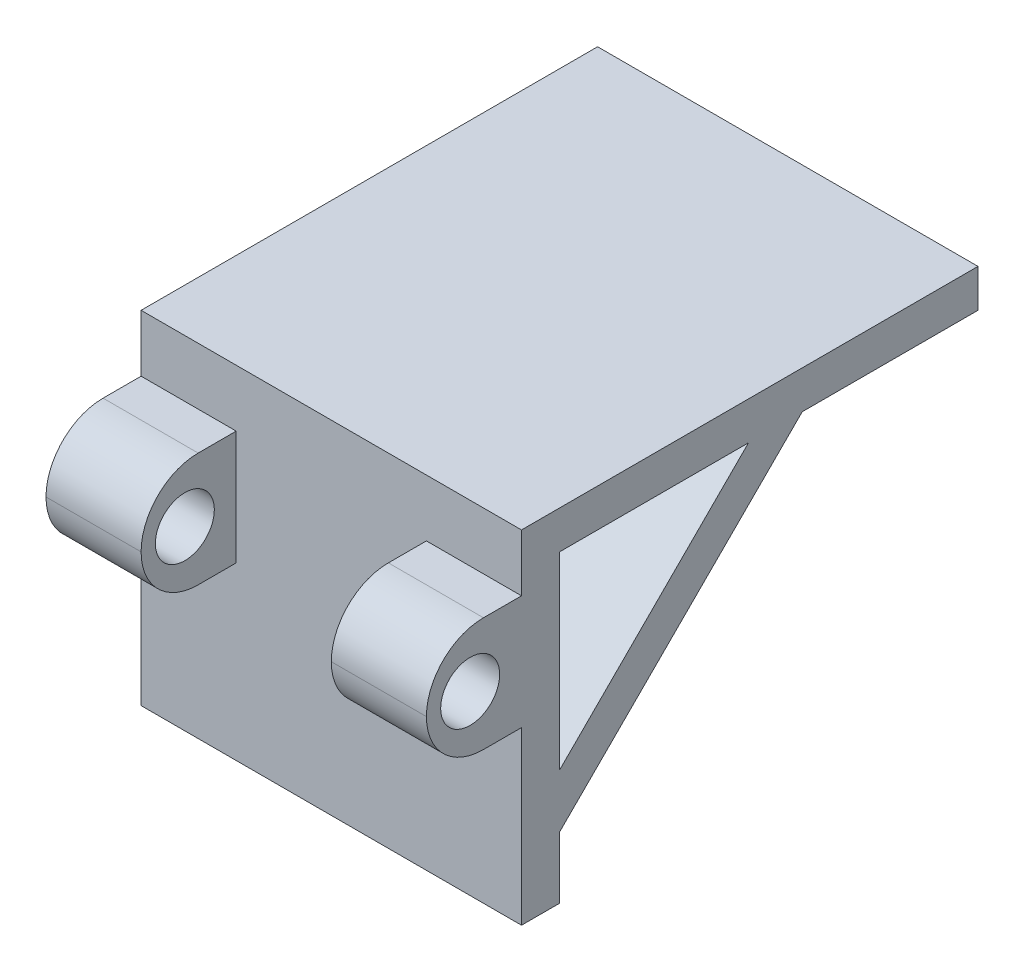
SolidWorks part; units mm, degrees
ref_plane "Front Plane" through (0, 0, 0) normal (0, 0, 1) x (1, 0, 0)
ref_plane "Top Plane" through (0, 0, 0) normal (0, 1, 0) x (1, 0, 0)
ref_plane "Right Plane" through (0, 0, 0) normal (1, 0, 0) x (0, 0, -1)
sketch "Sketch1" plane through (0, 0, 0) normal (0, 0, 1) x (1, 0, 0)
  line L0 (0, 0) -> (0, 7.5) construction
  line L1 (-10, -7.5) -> (10, -7.5)
  line L2 (-10, -7.5) -> (-10, 7.5)
  line L3 (-10, 7.5) -> (10, 7.5)
  line L4 (10, -7.5) -> (10, 7.5)
  line L5 (-10, -7.5) -> (10, 7.5) construction
  line L6 (-10, 7.5) -> (10, -7.5) construction
  line L7 (-5, 7.5) -> (5, 7.5)
  line L8 (-5, 7.5) -> (-5, 0)
  line L9 (-5, 0) -> (5, 0)
  line L10 (5, 7.5) -> (5, 0)
  point P0 (0, 0)
  dimension "D1" = 15
  dimension "D2" = 10
  dimension "D3" = 20
extrude "Boss-Extrude1" add sketch "Sketch1" along normal blind 5 contours L3 L10 L9 L8 L2 L1 L4 region at (0, -1.25, 0)
extrude "Boss-Extrude2" add sketch "Sketch1<3>" against normal blind 2 contours L3 L10 L9 L8 L2 L1 L4 | L10 L3 L8 L9 region at (0, -1.25, 0) region at (0, 3.75, 0)
sketch "Sketch1<3>" plane through (0, 0, 0) normal (0, 0, 1) x (1, 0, 0) same geometry as "Sketch1"
sketch "Sketch2" plane through (10, 0, 0) normal (1, 0, 0) x (0, 0, -1)
  line L0 (-5, 7.5) -> (0, 7.5) construction
  line L1 (-5, 7.5) -> (0, 7.5)
  line L2 (0, 7.5) -> (0, -15) construction
  circle A0 centre (-2.7, 4.5) radius 1.55
  dimension "D1" = 3.1
  dimension "D2" = 3
  dimension "D3" = 2.7
extrude "Cut-Extrude1" cut sketch "Sketch2" against normal through all contours A0 region at (10, 4.5, 2.7)
sketch "Sketch3" plane through (0, 0, 5) normal (0, 0, 1) x (1, 0, 0)
  line L0 (10, 1.5) -> (-10, 1.5)
  line L2 (-10, -7.5) -> (-10, 7.5) construction
  line L3 (10, -7.5) -> (10, 7.5) construction
  line L8 (10, 7.5) -> (5, 7.5)
  line L9 (5, 7.5) -> (5, 0)
  line L10 (5, 0) -> (-5, 0)
  line L11 (-5, 0) -> (-5, 7.5)
  line L12 (-5, 7.5) -> (-10, 7.5)
  line L13 (-10, 7.5) -> (-10, -7.5)
  line L14 (-10, -7.5) -> (10, -7.5)
  line L15 (10, -7.5) -> (10, 7.5)
  line L16 (10, 7.5) -> (5, 7.5) construction
  line L17 (5, 1.5) -> (5, 0)
  line L18 (5, 0) -> (-5, 0)
  line L19 (-5, 0) -> (-5, 1.5)
  line L20 (-5, 7.5) -> (-10, 7.5) construction
  line L21 (-10, 1.5) -> (-10, -7.5)
  line L22 (-10, -7.5) -> (10, -7.5)
  line L23 (10, -7.5) -> (10, 1.5)
  line M11 (5, 7.5) -> (5, 0)
  line M12 (5, 0) -> (-5, 0)
  line M13 (-5, 0) -> (-5, 7.5)
  line M15 (-10, 7.5) -> (-10, -7.5)
  line M16 (-10, -7.5) -> (10, -7.5)
  line M17 (10, -7.5) -> (10, 7.5)
  dimension "D2" = 6
  dimension "D1" = 0
extrude "Cut-Extrude3" cut sketch "Sketch3" against normal up to surface (5 mm away) contours L0 M17 M11 M12 M13 M15 M16 region at (0, -3.3409, 5) up to face at (0, 3.75, 0)
fillet "Fillet1" radius 3 4 edges at (-7.5, 1.5, 5) (-7.5, 7.5, 5) (7.5, 7.5, 5) (7.5, 1.5, 5)
sketch "Sketch4" plane through (0, 7.5, 0) normal (0, 1, 0) x (1, 0, 0)
  line L0 (-5, 0) -> (5, 0) construction
  line L1 (-10, -2) -> (-10, 2) construction
  line L2 (10, -2) -> (10, 2) construction
  line L3 (-10, 2) -> (10, 2) construction
  line L4 (-5, 0) -> (5, 0)
  line L5 (-10, 0) -> (-10, 2)
  line L6 (10, 0) -> (10, 2)
  line L7 (-10, 2) -> (10, 2)
  line L8 (5, 0) -> (10, 0)
  line L9 (-5, 0) -> (-10, 0)
extrude "Boss-Extrude3" add sketch "Sketch4" along normal blind 3
sketch "Sketch5" plane through (0, 0, -2) normal (0, 0, -1) x (-1, 0, 0)
  line L0 (-10, 10.5) -> (10, 10.5) construction
  line L1 (-10, 10.5) -> (10, 10.5)
  line L2 (-10, 10.5) -> (-10, 8.5)
  line L3 (-10, -7.5) -> (-10, 10.5) construction
  line L4 (-10, 8.5) -> (10, 8.5)
  line L5 (10, -7.5) -> (10, 10.5) construction
  line L6 (10, 8.5) -> (10, 10.5)
  dimension "D1" = 2
extrude "Boss-Extrude4" add sketch "Sketch5" along normal blind 22
sketch "Sketch6" plane through (0, 0, -2) normal (0, 0, -1) x (-1, 0, 0)
  line L0 (0, -7.5) -> (0, 8.5) construction
  line L1 (10, -7.5) -> (-10, -7.5) construction
  line L2 (-10, 8.5) -> (10, 8.5) construction
  line L3 (-10, -7.5) -> (-10, 8.5) construction
  circle A0 centre (-7, -4.5) radius 1.5
  circle A1 centre (7, -4.5) radius 1.5
  point P12 (0, 0)
  dimension "D1" = 3
  dimension "D2" = 3
  dimension "D3" = 3
sketch "Sketch7" plane through (0, 8.5, 0) normal (0, -1, 0) x (1, 0, 0)
  line L0 (0, -24) -> (0, -2) construction
  line L1 (10, -24) -> (-10, -24) construction
  line L2 (10, -24) -> (10, -2) construction
  circle A0 centre (7, -21) radius 1.5
  circle A1 centre (-7, -21) radius 1.5
  dimension "D1" = 3
  dimension "D2" = 3
  dimension "D3" = 3
sketch "Sketch8" plane through (10, 0, 0) normal (1, 0, 0) x (0, 0, -1)
  line L0 (14.7571, 8.5) -> (11.9346, 8.5)
  line L1 (24, 8.5) -> (2, 8.5) construction
  line L2 (11.9346, 8.5) -> (2, -1.4346)
  line L3 (2, -7.5) -> (2, 8.5) construction
  line L4 (2, -1.4346) -> (2, -4.2571)
  line L5 (2, -4.2571) -> (14.7571, 8.5)
  dimension "D1" = 1.9958
extrude "Boss-Extrude5" add sketch "Sketch8" against normal up to surface (20 mm away) up to face at (-10, 4.1364, -3.7961)
